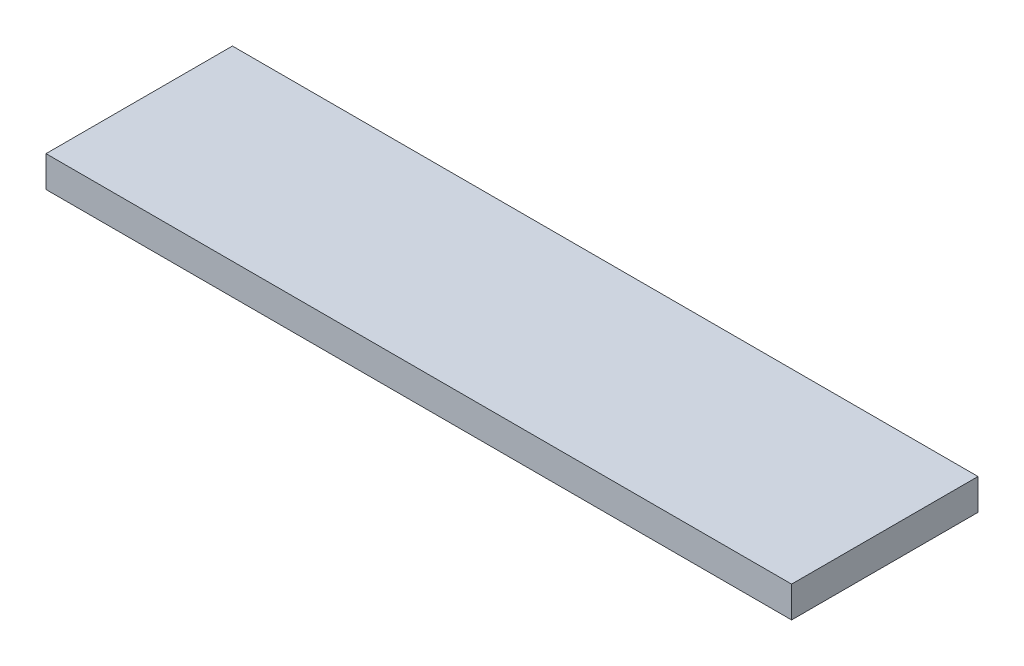
SolidWorks part; units mm, degrees
ref_plane "Спереди" through (0, 0, 0) normal (0, 0, 1) x (1, 0, 0)
ref_plane "Сверху" through (0, 0, 0) normal (0, 1, 0) x (1, 0, 0)
ref_plane "Справа" through (0, 0, 0) normal (1, 0, 0) x (0, 0, -1)
sketch "Эскиз2" plane through (0, 0, 0) normal (0, 1, 0) x (1, 0, 0)
  line L1 (-240, 60) -> (240, 60)
  line L3 (-240, -60) -> (240, -60)
  line L4 (240, 60) -> (240, -60)
  line L5 (-240, 60) -> (240, -60) construction
  line L6 (-240, -60) -> (240, 60) construction
  line L7 (-240, -60) -> (-240, 60)
  line L8 (-133.3374, 0) -> (121.3538, 0) construction
  point P0 (0, 0)
extrude "Бобышка-Вытянуть1" add sketch "Эскиз2" along normal blind 20
